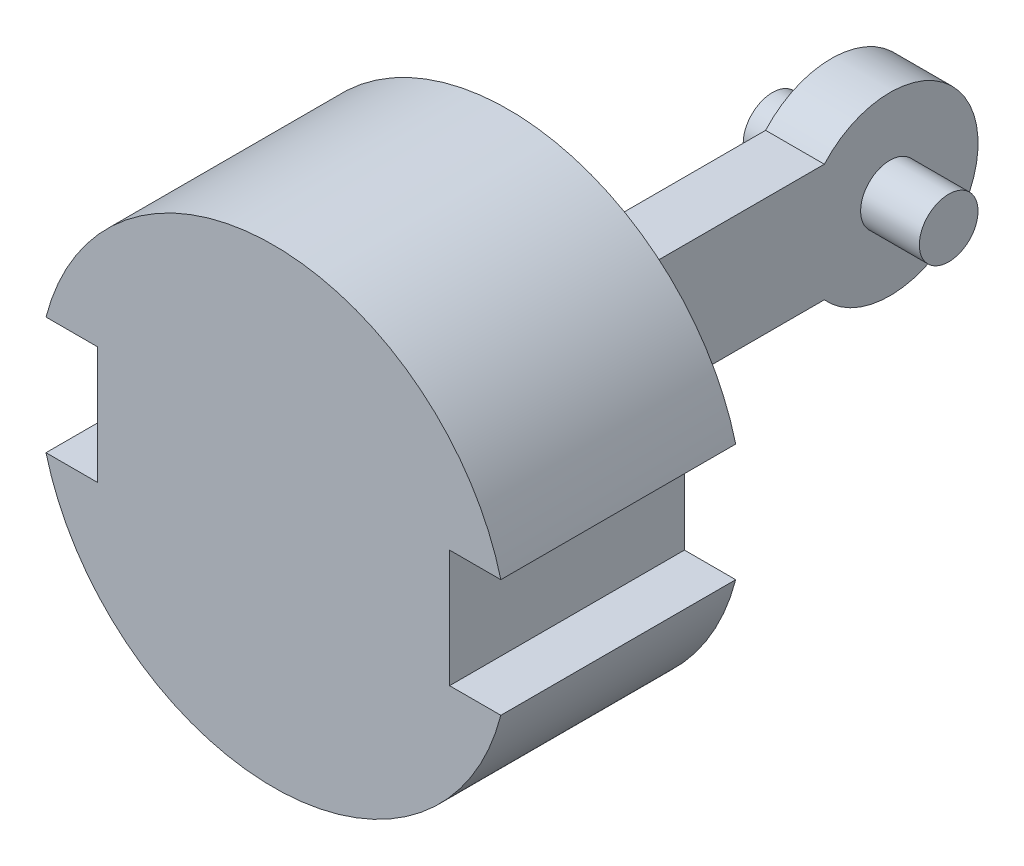
SolidWorks part; units mm, degrees
material "1060 Alloy"
ref_plane "Front Plane" through (0, 0, 0) normal (0, 0, 1) x (1, 0, 0)
ref_plane "Top Plane" through (0, 0, 0) normal (0, 1, 0) x (1, 0, 0)
ref_plane "Right Plane" through (0, 0, 0) normal (1, 0, 0) x (0, 0, -1)
sketch "Sketch1" plane through (0, 0, 0) normal (0, 0, 1) x (1, 0, 0)
  line L1 (-63.5, -12.7) -> (-38.1, -12.7)
  line L2 (-63.5, -12.7) -> (-63.5, 12.7)
  line L3 (-63.5, 12.7) -> (-38.1, 12.7)
  line L4 (-38.1, -12.7) -> (-38.1, 12.7)
  line L5 (-63.5, -12.7) -> (-38.1, 12.7) construction
  line L6 (-63.5, 12.7) -> (-38.1, -12.7) construction
  line L7 (38.1, -12.7) -> (63.5, -12.7)
  line L8 (38.1, -12.7) -> (38.1, 12.7)
  line L9 (38.1, 12.7) -> (63.5, 12.7)
  line L10 (63.5, -12.7) -> (63.5, 12.7)
  line L11 (38.1, -12.7) -> (63.5, 12.7) construction
  line L12 (38.1, 12.7) -> (63.5, -12.7) construction
  line L13 (-6.35, -12.7) -> (6.35, -12.7)
  line L14 (-6.35, -12.7) -> (-6.35, 12.7)
  line L15 (-6.35, 12.7) -> (6.35, 12.7)
  line L16 (6.35, -12.7) -> (6.35, 12.7)
  line L17 (-6.35, -12.7) -> (6.35, 12.7) construction
  line L18 (-6.35, 12.7) -> (6.35, -12.7) construction
  circle A0 centre (0, 0) radius 50.8
  point P3 (-50.8, 0)
  point P8 (50.8, 0)
  dimension "D1" = 101.6
  dimension "D3" = 12.7
  dimension "D2" = 12.7
  dimension "D4" = 25.4
  dimension "D5" = 25.4
  dimension "D6" = 12.7
  dimension "D7" = 25.4
extrude "Boss-Extrude1" add sketch "Sketch1" against normal blind 50.8 contours L9 A0 L3 L4 L1 L7 L8 L16 L13 L14 L15 region at (-43.6434, -14.1142, 0)
extrude "Boss-Extrude2" add sketch "Sketch1<3>" against normal blind 127 contours L13 L16 L15 L14 region at (0, 0, 0)
sketch "Sketch1<3>" plane through (0, 0, 0) normal (0, 0, 1) x (1, 0, 0) same geometry as "Sketch1"
sketch "Sketch2" plane through (6.35, 0, 0) normal (1, 0, 0) x (0, 0, -1)
  line L0 (127, -12.7) -> (127, 12.7) construction
  circle A0 centre (127, 0) radius 6.35
  circle A1 centre (127, 0) radius 19.05
  line M3 (127, -12.7) -> (127, 12.7)
  dimension "D1" = 38.1
  dimension "D2" = 12.7
extrude "Boss-Extrude3" add sketch "Sketch2" against normal blind 12.7
extrude "Boss-Extrude4" add sketch "Sketch2<2>" along normal mid plane 38.1 from offset 6.35 contours A0 M3 | A0 M3 region at (6.35, 0, -129.695) region at (6.35, 0, -124.305) offset against normal yes
sketch "Sketch2<2>" plane through (6.35, 0, 0) normal (1, 0, 0) x (0, 0, -1) same geometry as "Sketch2"
